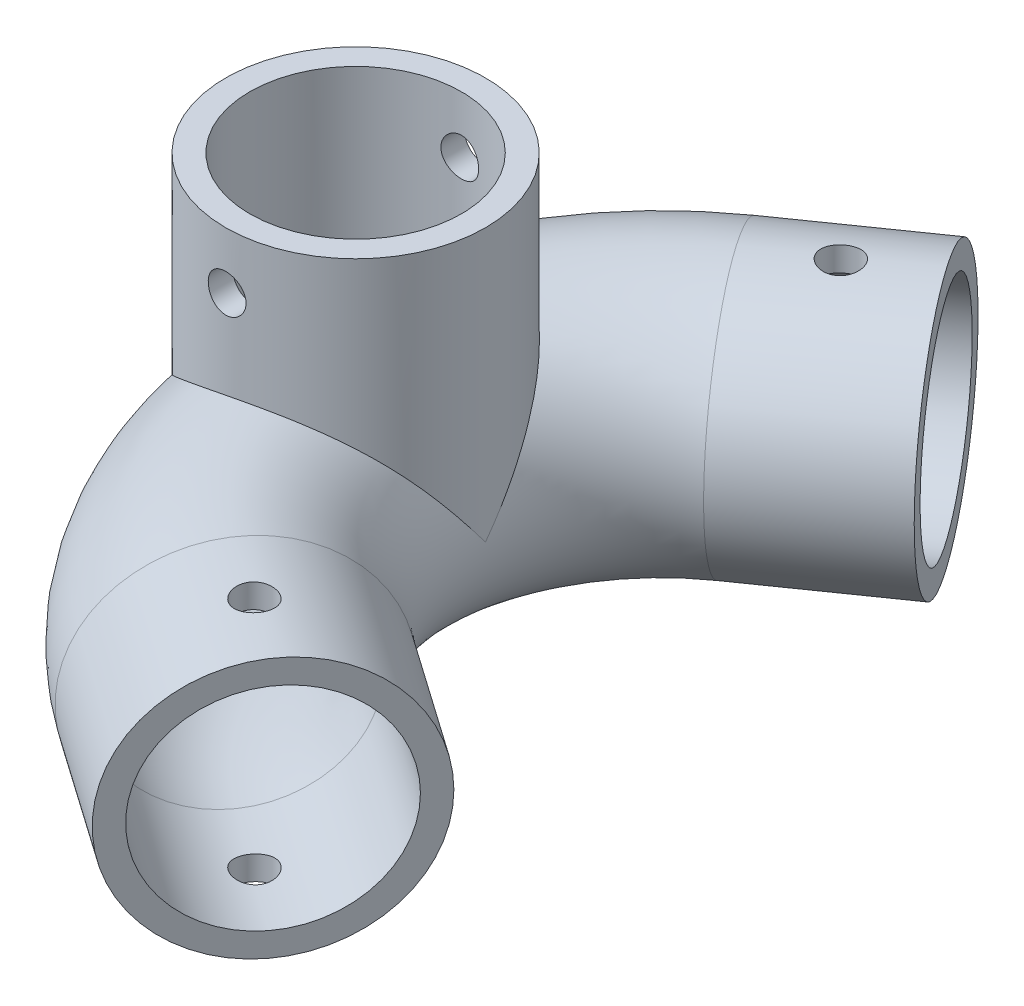
SolidWorks part; units mm, degrees
material "1060 Alloy"
ref_plane "Front Plane" through (0, 0, 0) normal (0, 0, 1) x (1, 0, 0)
ref_plane "Top Plane" through (0, 0, 0) normal (0, 1, 0) x (1, 0, 0)
ref_plane "Right Plane" through (0, 0, 0) normal (1, 0, 0) x (0, 0, -1)
sketch "Sketch1" plane through (0, 0, 0) normal (0, 1, 0) x (1, 0, 0)
  line L0 (-70.3338, 0) -> (-6.7453, 44.512) construction
  line L1 (-70.3338, 0) -> (-6.7453, -44.512) construction
  line L2 (-23.1299, 33.0427) -> (-6.7453, 44.512)
  line L3 (-23.1299, -33.0427) -> (-6.7453, -44.512)
  arc A0 (-23.1299, 33.0427) -> (-23.1299, -33.0427) centre (0, 0) ccw
  point P1 (-40.3338, 0)
  dimension "D5" = 30
  dimension "D6" = 20
  dimension "D1" = 69.984
sketch "Sketch2" plane through (0, 0, 0) normal (0, 0, 1) x (1, 0, 0)
  line L2 (-70.3338, 0) -> (-6.7453, 0) construction
  line L4 (-23.1299, 0) -> (-40.3338, 0) construction
  circle A1 centre (-40.3338, 0) radius 17.175
  dimension "D1" = 34.35
  dimension "D2" = 30
sweep "Sweep1" add profiles "Sketch2" path "Sketch1"
sketch "Sketch3" plane through (16.3846, 0, 11.4692) normal (0.8192, 0, 0.5735) x (0.5735, 0, -0.8192)
  circle A0 centre (-40.3338, 0) radius 17.675
  circle A1 centre (-40.3338, 0) radius 17.175 construction
  dimension "D1" = 0.5
sketch "Sketch7" plane through (0, 0, 0) normal (0, 1, 0) x (1, 0, 0)
  line L0 (-6.7453, 44.512) -> (-40.3338, 0) construction
  line L1 (3.104, 30.4416) -> (-16.5945, 58.5823) construction
  line L2 (-40.3338, 0) -> (-6.7453, -44.512) construction
  line L3 (-16.8812, -58.9919) -> (3.3907, -30.032) construction
  line L4 (-57.5088, 0) -> (-23.1588, 0) construction
  circle A0 centre (-40.3338, 0) radius 17.175
  arc A1 (-32.9791, 47.113) -> (-32.9791, -47.113) centre (0, 0) ccw construction
  arc A2 (-13.2807, 18.9724) -> (-13.2807, -18.9724) centre (0, 0) ccw construction
  point P9 (-40.3338, 0)
  dimension "D1" = 34.35
extrude "Boss-Extrude2" add sketch "Sketch7" along normal blind 36 contours A0
shell "Shell1" thickness 3.175 removed face at (-40.3338, 36, 17.175) removed face at (3.104, 0, -30.4416) removed face at (3.104, 0, 30.4416)
sketch "Sketch8" plane through (0, 0, 0) normal (0, 0, 1) x (1, 0, 0)
  line L0 (-40.3338, 36) -> (-40.3338, 28.5) construction
  line L1 (-26.3338, 36) -> (-54.3338, 36) construction
  circle A0 centre (-40.3338, 28.5) radius 2.5
  dimension "D1" = 5
  dimension "D2" = 7.5
extrude "Cut-Extrude1" cut sketch "Sketch8" against normal through all both and the other way through all
sketch "Sketch9" plane through (0, 0, 0) normal (0, 1, 0) x (1, 0, 0)
  line L0 (-6.7453, 44.512) -> (-14.9376, 38.7773) construction
  line L1 (1.2832, 33.0427) -> (-14.7737, 55.9812) construction
  line L2 (-29.3249, 0) -> (29.3249, 0) construction
  circle A0 centre (-14.9376, 38.7773) radius 2.5
  circle A1 centre (-14.9376, -38.7773) radius 2.5
  dimension "D2" = 5
  dimension "D1" = 10
extrude "Cut-Extrude2" cut sketch "Sketch9" against normal through all both and the other way through all
equation "\"keelOutDiameter\"= 1in"
equation "\"poleOutDiameter\"= 28mm"
equation "\"poleLength\"=650mm"
equation "\"propellerTubeOutDiameter\"= 28mm"
equation "\"D1@Sketch2\"=\"propellerTubeOutDiameter\"+0.25in"
equation "\"D1@Sketch7\"=\"poleOutDiameter\"+0.25in"
equation "\"propellerDiameter\"= 700mm"
equation "\"D1@Sketch1\"=arccotan( 500mm / ( \"propellerDiameter\" / 2 ) ) *2"
